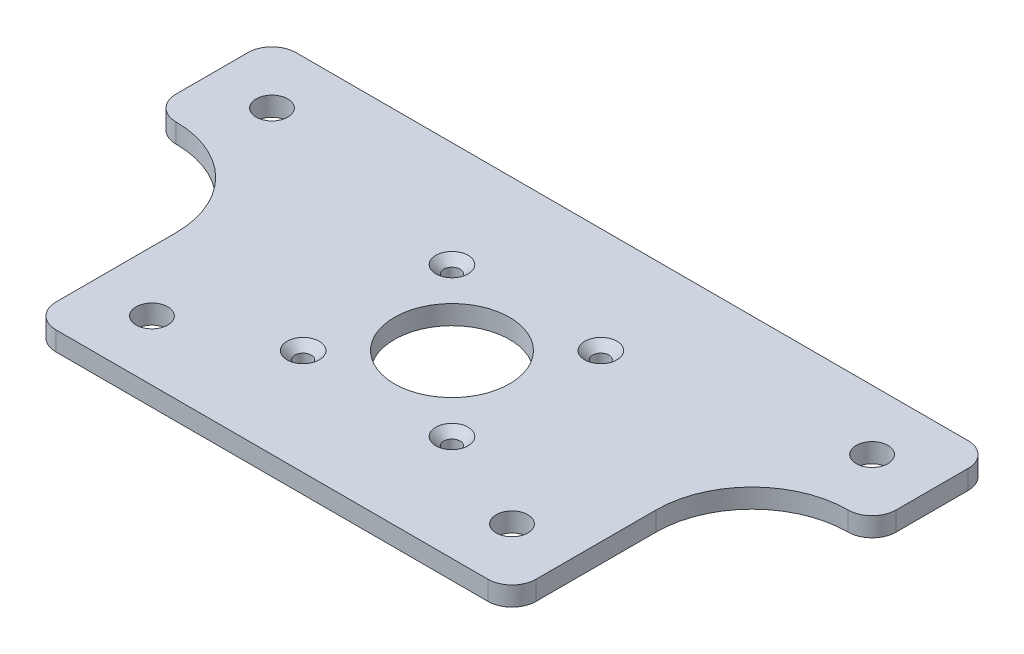
SolidWorks part; units mm, degrees
material "6061-T6 (SS)"
ref_plane "Front Plane" through (0, 0, 0) normal (0, 0, 1) x (1, 0, 0)
ref_plane "Top Plane" through (0, 0, 0) normal (0, 1, 0) x (1, 0, 0)
ref_plane "Right Plane" through (0, 0, 0) normal (1, 0, 0) x (0, 0, -1)
sketch "Sketch1" plane through (0, 0, 0) normal (0, 1, 0) x (1, 0, 0)
  line L0 (-37.5, 25) -> (-37.5, -25) construction
  line L1 (50, -37.5) -> (-50, -37.5)
  line L2 (50, -37.5) -> (50, 37.5) construction
  line L3 (50, 37.5) -> (-50, 37.5)
  line L4 (-50, -37.5) -> (-50, 37.5) construction
  line L5 (50, -37.5) -> (-50, 37.5) construction
  line L6 (50, 37.5) -> (-50, -37.5) construction
  line L7 (-37.5, -25) -> (37.5, -25) construction
  line L8 (37.5, -25) -> (37.5, 25) construction
  line L9 (37.5, 25) -> (-37.5, 25) construction
  line L10 (-37.5, -25) -> (37.5, 25) construction
  line L11 (-50, -37.5) -> (-50, 12.5)
  line L12 (15.5, -15.5) -> (-15.5, -15.5) construction
  line L13 (15.5, -15.5) -> (15.5, 15.5) construction
  line L14 (15.5, 15.5) -> (-15.5, 15.5) construction
  line L15 (-15.5, -15.5) -> (-15.5, 15.5) construction
  line L16 (15.5, -15.5) -> (-15.5, 15.5) construction
  line L17 (15.5, 15.5) -> (-15.5, -15.5) construction
  line L18 (-50, 37.5) -> (-75, 37.5)
  line L19 (-50, 37.5) -> (-50, 12.5)
  line L20 (-50, 12.5) -> (-75, 12.5)
  line L21 (-75, 37.5) -> (-75, 12.5)
  line L22 (50, 37.5) -> (75, 37.5)
  line L23 (50, 37.5) -> (50, 12.5)
  line L24 (50, 12.5) -> (75, 12.5)
  line L25 (75, 37.5) -> (75, 12.5)
  line L26 (50, -37.5) -> (50, 12.5)
  circle A0 centre (0, 0) radius 12
  point P0 (0, 0)
  point P6 (-37.5, 25)
  point P9 (37.5, 25)
  point P10 (-37.5, -25)
  point P11 (37.5, -25)
  point P14 (0, 0)
  point P24 (75, 25)
  point P28 (62.5, 25)
  point P30 (-62.5, 25)
  dimension "D3" = 24
  dimension "D1" = 100
  dimension "D2" = 75
  dimension "D4" = 75
  dimension "D5" = 31
  dimension "D6" = 25
  dimension "D7" = 25
  dimension "D8" = 25
  dimension "D11" = 50
extrude "Boss-Extrude1" add sketch "Sketch1" along normal blind 4 contours L18 L21 L20 L4 | L4 L1 L2 L3 A0 | L25 L22 L2 L24 region at (0, 0, 36.25) region at (62.5, 0, -25) region at (-62.5, 0, -25)
sketch "Sketch5" plane through (0, 4, 0) normal (0, -1, 0) x (1, 0, 0)
  line L0 (50, -37.5) -> (-50, 37.5) construction
  line L1 (37.5, -25) -> (-37.5, -25)
  line L2 (37.5, -25) -> (37.5, 25)
  line L3 (37.5, 25) -> (-37.5, 25)
  line L12 (-37.5, -25) -> (-37.5, 25)
  line L13 (37.5, -25) -> (-37.5, 25) construction
  line L14 (37.5, 25) -> (-37.5, -25) construction
  line L16 (15.5, -15.5) -> (-15.5, -15.5)
  line L17 (15.5, -15.5) -> (15.5, 15.5)
  line L18 (15.5, 15.5) -> (-15.5, 15.5)
  line L19 (-15.5, -15.5) -> (-15.5, 15.5)
  line L20 (15.5, -15.5) -> (-15.5, 15.5) construction
  line L21 (15.5, 15.5) -> (-15.5, -15.5) construction
  point P0 (62.5, -25)
  point P1 (-62.5, -25)
  point P2 (0, 0)
  point P12 (0, 0)
hole_wizard "CSK for M3 Hex Socket Countersunk Cap Screw1" positions "3DSketch7" profile "Sketch9" countersink size "M3" standard "ISO" end condition up to next
sketch3d "3DSketch7"
  point P0 (-15.5, 4, 15.5)
  point P3 (15.5, 4, 15.5)
  point P6 (15.5, 4, -15.5)
  point P9 (-15.5, 4, -15.5)
sketch "Sketch9" plane through (-15.5, 4, 15.5) normal (1, 0, 0) x (0, 0, 1)
  line L0 (0, 0) -> (0, 4)
  line L1 (0, 4) -> (1.7, 4)
  line L2 (1.7, 4) -> (1.7, 1.66)
  line L3 (1.7, 1.66) -> (3.36, 0)
  line L5 (3.36, 0) -> (0, 0)
  line L6 (-1.7, 1.66) -> (-3.36, 0) construction
  line L11 (0, -6.35) -> (0, 107.95) construction
  dimension "Thru Hole Dia." = 3.4
  dimension "Thru Hole Depth" = 4
  dimension "Near C'Sink Dia." = 6.72
  dimension "Near C'Sink Angle" = 90
hole_wizard "M6 Clearance Hole2" positions "Sketch10" profile "Sketch11" hole size "M6" standard "ISO" end condition up to next
sketch "Sketch10" plane through (0, 0, 0) normal (0, -1, 0) x (-1, 0, 0)
  point P0 (62.5, 25)
  point P3 (37.5, -25)
  point P6 (-37.5, -25)
  point P9 (-62.5, 25)
sketch "Sketch11" plane through (-62.5, 0, -25) normal (1, 0, 0) x (0, 0, -1)
  line L0 (0, 0) -> (0, 4)
  line L1 (0, 4) -> (3.3, 4)
  line L2 (3.3, 4) -> (3.3, 0)
  line L5 (3.3, 0) -> (0, 0)
  line L11 (0, -6.35) -> (0, 107.95) construction
  dimension "Thru Hole Dia." = 6.6
  dimension "Thru Hole Depth" = 4
fillet "Fillet1" radius 5 6 edges at (75, 2, -37.5) (75, 2, -12.5) (50, 2, 37.5) (-50, 2, 37.5) (-75, 2, -12.5) (-75, 2, -37.5)
fillet "Fillet2" radius 20 2 edges at (50, 2, -12.5) (-50, 2, -12.5)
sketch "Sketch12" plane through (0, 4, 0) normal (0, 1, 0) x (1, 0, 0)
  line L0 (-37.5, 25) -> (37.5, 25) construction
  circle A0 centre (-62.5, 25) radius 3.3 construction
  circle A1 centre (-62.5, 25) radius 3.3 construction
  circle A2 centre (-37.5, 25) radius 6
  circle A3 centre (37.5, 25) radius 6
  point P7 (0, 25)
  dimension "D2" = 12
  dimension "D1" = 25
extrude "Cut-Extrude1" [suppressed] cut sketch "Sketch12" against normal through all
